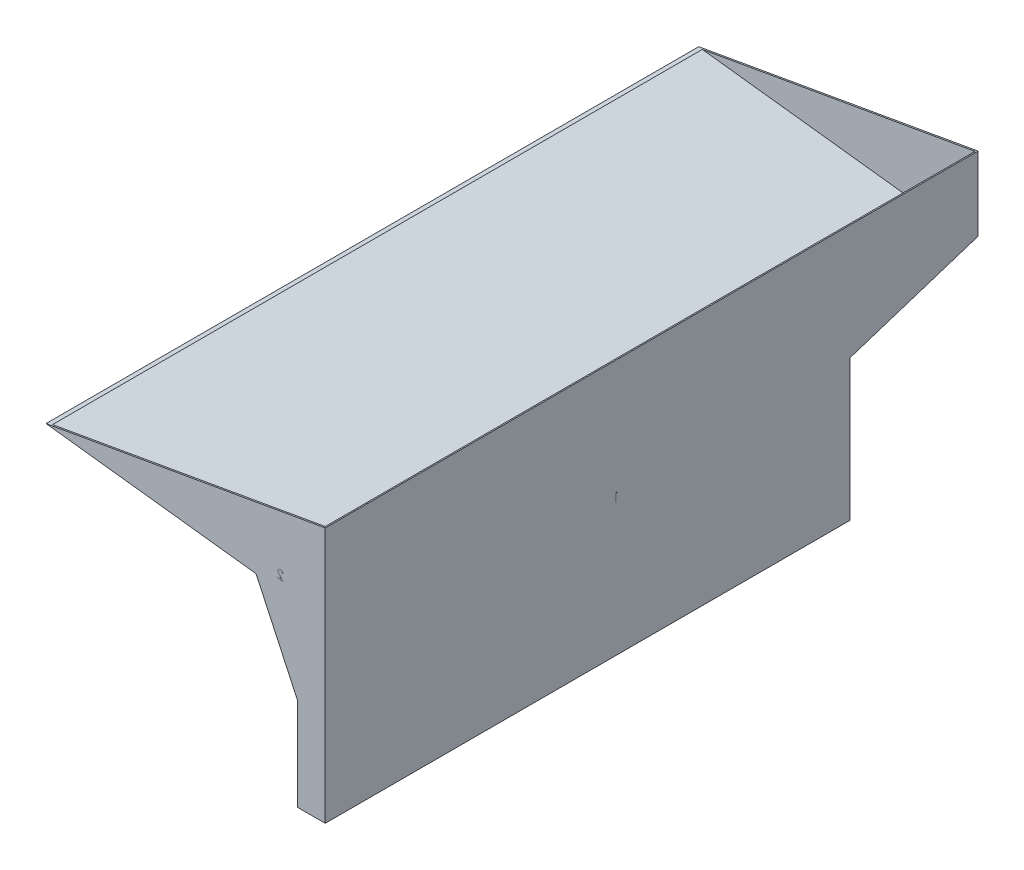
SolidWorks part; units mm, degrees
material "Melamine"
ref_plane "Front Plane" through (0, 0, 0) normal (0, 0, 1) x (1, 0, 0)
ref_plane "Top Plane" through (0, 0, 0) normal (0, 1, 0) x (1, 0, 0)
ref_plane "Right Plane" through (0, 0, 0) normal (1, 0, 0) x (0, 0, -1)
other "Center of Mass"
sketch "Sketch2" plane through (0, 0, 0) normal (0, 0, 1) x (1, 0, 0)
  line L0 (0, 0) -> (-88.7498, 190.3246)
  line L1 (-88.7498, 190.3246) -> (-540.3388, 244.1441)
  line L2 (-540.3388, 244.1441) -> (60, 350)
  line L3 (60, 350) -> (60, -200)
  line L4 (60, -200) -> (0, -200)
  line L5 (0, -200) -> (0, 0)
  dimension "D1" = 155
  dimension "D2" = 609.6
  dimension "D3" = 550
  dimension "D4" = 200
  dimension "D5" = 60
  dimension "D6" = 210
  dimension "D7" = 280
extrude "Boss-Extrude1" add sketch "Sketch2" along normal mid plane 1403.35
shell "Shell1" thickness 3.175 removed face at (-240.1694, 297.072, 0)
sketch "Sketch3" plane through (0, 0, 701.675) normal (0, 0, 1) x (1, 0, 0)
  line L1 (9, -187.3) -> (51, -187.3)
  line L2 (9, -187.3) -> (9, 102.7)
  line L3 (9, 102.7) -> (51, 102.7)
  line L4 (51, -187.3) -> (51, 102.7)
  line L6 (0, -200) -> (60, -200) construction
  point P6 (30, -200)
  point P7 (30, -187.3)
  dimension "D1" = 42
  dimension "D2" = 12.7
  dimension "D3" = 290
extrude "Cut-Extrude1" cut sketch "Sketch3" against normal blind 20
sketch "Sketch7" plane through (0, 0, 0) normal (-1, 0, 0) x (0, 0, 1)
  line L1 (701.675, -200) -> (426.675, -200)
  line L2 (701.675, -200) -> (701.675, 102.7)
  line L3 (701.675, 102.7) -> (426.675, 102.7)
  line L4 (426.675, -200) -> (426.675, 102.7)
  dimension "D1" = 275
  dimension "D2" = 302.7
extrude "Cut-Extrude5" cut sketch "Sketch7" against normal mid plane 200
sketch "Sketch9" plane through (60, 0, 0) normal (1, 0, 0) x (0, 0, -1)
  line L1 (-426.675, 102.7) -> (-701.675, 102.7)
  line L2 (-426.675, 102.7) -> (-426.675, 191.216)
  line L3 (-426.675, 191.216) -> (-701.675, 191.216)
  line L4 (-701.675, 102.7) -> (-701.675, 191.216)
  line L5 (-701.675, 191.216) -> (-426.675, 102.7)
  line M2 (-701.675, 102.7) -> (-426.675, 102.7)
  line M7 (-701.675, 350) -> (-701.675, 102.7)
  dimension "D1" = 88.516
extrude "Cut-Extrude7" cut sketch "Sketch9" against normal through all contours L5 M7 M2 region at (60, 132.2053, 610.0083)
sketch "Sketch11" plane through (0, -31.385, 10.1021) normal (0, -0.9519, 0.3064) x (1, 0, 0)
  line L0 (60, 726.5152) -> (60, 437.6206)
  line L1 (60, 437.6206) -> (-47.8898, 437.6206)
  line L2 (-47.8898, 437.6206) -> (-86.0836, 726.5152)
  line L3 (-86.0836, 726.5152) -> (60, 726.5152)
  line L4 (-96.2291, 726.5152) -> (60, 726.5152) construction
  point P8 (0, 0)
  point P11 (-86.0836, 726.5152)
extrude "Boss-Extrude3" add sketch "Sketch11" against normal blind 3.175
sketch "Sketch12" plane through (3.175, 0, 0) normal (1, 0, 0) x (0, 0, -1)
  line L0 (-426.675, -196.825) -> (688.975, -79.5655)
  line L1 (688.975, -79.5655) -> (688.975, -82.7405)
  line L2 (-396.4669, -196.825) -> (-426.675, -196.825)
  line L3 (701.675, -200) -> (701.675, 350) construction
  line L4 (688.975, -82.7405) -> (-396.4669, -196.825)
  line L5 (-396.4669, -196.825) -> (-396.4669, -193.65)
  line M5 (-426.675, -196.825) -> (698.5, -196.825)
  dimension "D1" = 3.175
  dimension "D2" = 12.7
  dimension "D3" = 6
  dimension "D4" = 3.175
  dimension "D5" = 3.175
extrude "Boss-Extrude4" add sketch "Sketch12" along normal up to surface (53.65 mm away) contours L5 L4 L1 L0 | L5 L0 M5 region at (3.175, -195.7667, 406.5363) region at (3.175, -138.1952, -146.2541) up to face at (56.825, 101.026, 182.7217)
chamfer "Chamfer1" distance 6.35 angle 45 1 edges at (30, -196.825, 426.675) first distance on face at (30, -138.1952, -131.15)
sketch "Sketch14" plane through (60, 0, 0) normal (1, 0, 0) x (0, 0, -1)
  line L0 (-426.675, 102.7) -> (-426.675, -200) construction
  line L1 (-426.675, -200) -> (701.675, -200) construction
  text T0 "1" font "Century Gothic" height in points 72
  dimension "D1" = 496.5296
  dimension "D2" = 284.9328
extrude "Cut-Extrude8" cut sketch "Sketch14" against normal blind 0.1
sketch "Sketch15" plane through (0, 0, -701.675) normal (0, 0, -1) x (-1, 0, 0)
  text T0 "2" font "Century Gothic" height in points 72
extrude "Cut-Extrude9" cut sketch "Sketch15" against normal blind 0.1
sketch "Sketch16" plane through (21.1219, 177.2303, 0) normal (-0.1183, -0.993, 0) x (0.993, -0.1183, 0)
  text T0 "3" font "Century Gothic" height in points 72
extrude "Cut-Extrude10" cut sketch "Sketch16" against normal blind 0.1
sketch "Sketch17" plane through (0, 0, 0) normal (-0.9063, -0.4226, 0) x (0, 0, 1)
  text T0 "4" font "Century Gothic" height in points 72
extrude "Cut-Extrude11" cut sketch "Sketch17" against normal blind 0.1
sketch "Sketch18" plane through (0, 0, 0) normal (-1, 0, 0) x (0, 0, 1)
  text T0 "5" font "Century Gothic" height in points 72
extrude "Cut-Extrude12" cut sketch "Sketch18" against normal blind 0.1
sketch "Sketch19" plane through (0, -200, 0) normal (0, -1, 0) x (1, 0, 0)
  text T0 "6" font "Century Gothic" height in points 72
extrude "Cut-Extrude13" cut sketch "Sketch19" against normal blind 0.1
sketch "Sketch20" plane through (0, -31.385, 10.1021) normal (0, -0.9519, 0.3064) x (1, 0, 0)
  text T0 "7" font "Century Gothic" height in points 72
extrude "Cut-Extrude14" cut sketch "Sketch20" against normal blind 0.1
sketch "Sketch21" plane through (0, 0, 701.675) normal (0, 0, 1) x (1, 0, 0)
  text T0 "8" font "Century Gothic" height in points 72
extrude "Cut-Extrude15" cut sketch "Sketch21" against normal blind 0.1
mirror "Mirror1" about plane through (0, 0, -701.675) normal (0, 0, 1) of bodies 122
sketch "Sketch22" plane through (0, 0, 0) normal (-1, 0, 0) x (0, 0, 1)
  line L5 (-701.675, -200) -> (1024.7166, -200)
  line L6 (-701.675, -200) -> (-701.675, 602.0407)
  line L7 (-701.675, 602.0407) -> (1024.7166, 602.0407)
  line L8 (1024.7166, -200) -> (1024.7166, 602.0407)
extrude "Cut-Extrude16" cut sketch "Sketch22" against normal through all both and the other way through all
